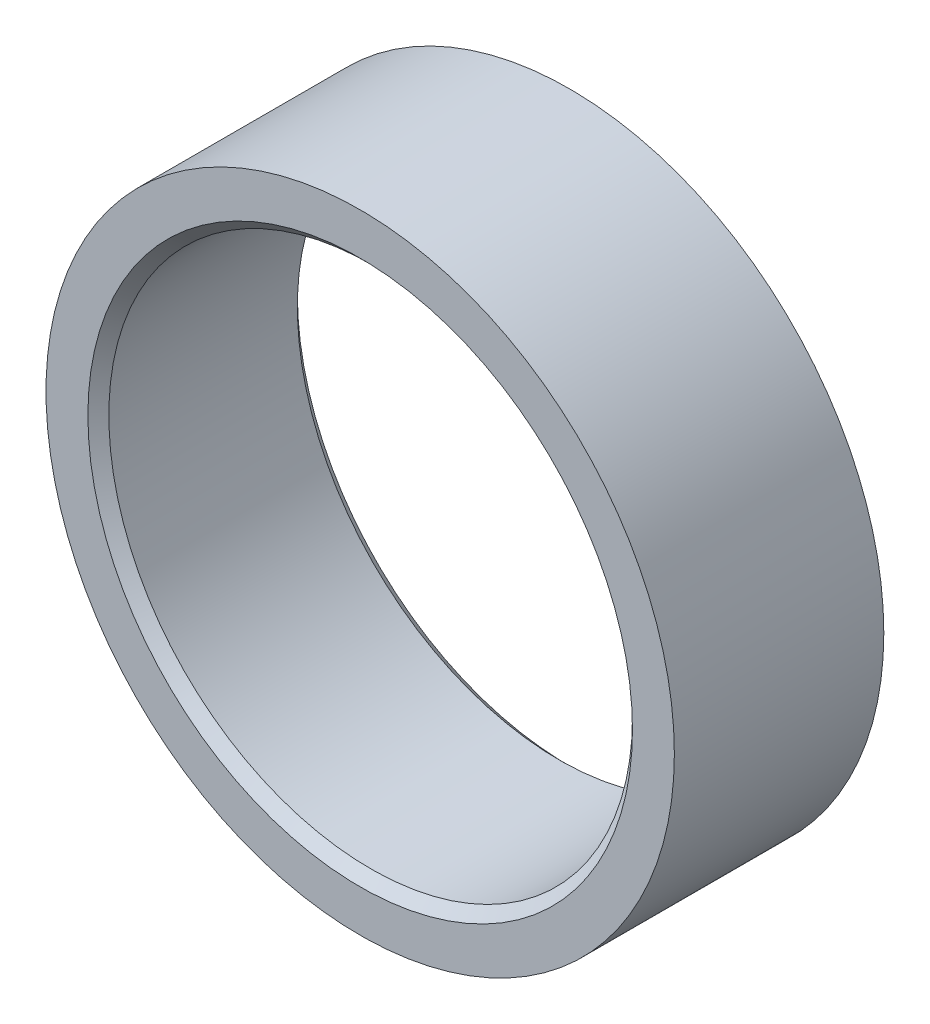
SolidWorks part; units mm, degrees
material "6061 合金"
ref_plane "前视基准面" through (0, 0, 0) normal (0, 0, 1) x (1, 0, 0)
ref_plane "上视基准面" through (0, 0, 0) normal (0, 1, 0) x (1, 0, 0)
ref_plane "右视基准面" through (0, 0, 0) normal (1, 0, 0) x (0, 0, -1)
other "Configuration Table"
sketch "草图1" plane through (0, 0, 0) normal (0, 0, 1) x (1, 0, 0)
  circle A0 centre (0, 0) radius 5
  circle A1 centre (0, 0) radius 6
  dimension "D1" = 10
  dimension "D2" = 12
extrude "凸台-拉伸1" add sketch "草图1" along normal blind 4 contours A0 | A1 region at (0, 0, 0)
sketch "草图2" plane through (0, 0, 0) normal (0, 0, -1) x (-1, 0, 0)
  circle A0 centre (0, 0) radius 7
  circle A1 centre (0, 0) radius 5 construction
  circle A2 centre (0, 0) radius 5
  dimension "D1" = 14
extrude "凸台-拉伸2" [suppressed] add sketch "草图2" against normal blind 1
sketch "草图3" [suppressed] plane through (0, 0, 15) normal (0, 0, 1) x (1, 0, 0)
  circle A1 centre (0, 0) radius 5 construction
  circle A2 centre (0, 0) radius 5
  circle A3 centre (0, 0) radius 7 construction
  circle A4 centre (0, 0) radius 7
extrude "凸台-拉伸3" [suppressed] add sketch "草图3" against normal blind 1
fillet "圆角1" [suppressed] radius 0.5
chamfer "倒角1" distance 0.2 angle 45 2 edges at (5, 0, 0) (5, 0, 4)
